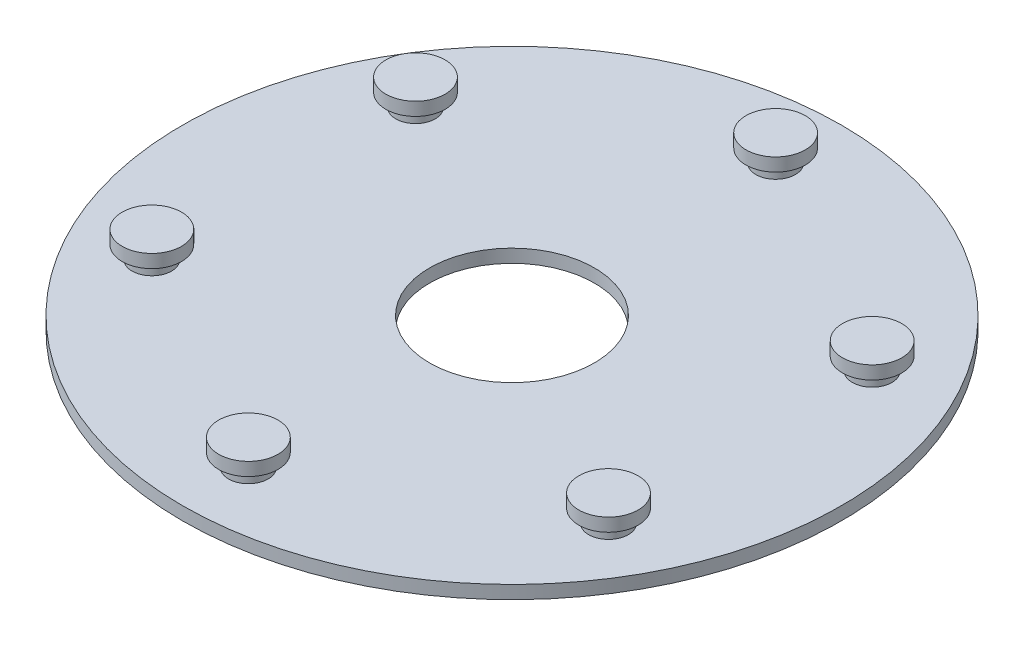
SolidWorks part; units mm, degrees
ref_plane "Front Plane" through (0, 0, 0) normal (0, 0, 1) x (1, 0, 0)
ref_plane "Top Plane" through (0, 0, 0) normal (0, 1, 0) x (1, 0, 0)
ref_plane "Right Plane" through (0, 0, 0) normal (1, 0, 0) x (0, 0, -1)
sketch "Sketch1" plane through (0, 0, 0) normal (0, 1, 0) x (1, 0, 0)
  circle A0 centre (0, 0) radius 50
  dimension "D1" = 100
extrude "Boss-Extrude1" add sketch "Sketch1" along normal blind 2 contours A0
sketch "Sketch2" plane through (0, 2, 0) normal (0, 1, 0) x (1, 0, 0)
  line L0 (0, 50) -> (0, -50) construction
  line L1 (-50, 0) -> (50, 0) construction
  circle A0 centre (0, 0) radius 50 construction
  circle A1 centre (0, -40) radius 4.5
  circle A2 centre (0, 0) radius 40 construction
  circle A3 centre (0, 0) radius 12.5
  circle A4 centre (0, -40) radius 3
  dimension "D1" = 80
  dimension "D2" = 25
  dimension "D3" = 9
  dimension "D4" = 6
extrude "Cut-Extrude1" cut sketch "Sketch2" against normal up to surface (2 mm away) contours A3 up to face at (0, 0, 50)
extrude "Boss-Extrude2" add sketch "Sketch2<3>" along normal blind 4 contours A1
sketch "Sketch2<3>" plane through (0, 2, 0) normal (0, 1, 0) x (1, 0, 0) same geometry as "Sketch2"
extrude "Cut-Extrude2" cut sketch "Sketch2<4>" along normal blind 2 contours A4 | A1
sketch "Sketch2<4>" plane through (0, 2, 0) normal (0, 1, 0) x (1, 0, 0) same geometry as "Sketch2"
pattern_circular "CirPattern1" count 12 every 30 about axis through (0, -35.3553, 0) along (0, 1, 0) skipping 1, 3, 5, 7, 9, 11 of "Boss-Extrude2", "Cut-Extrude2"
sketch "Sketch4" plane through (0, 2, 0) normal (0, 1, 0) x (1, 0, 0)
  line L0 (0, 50) -> (0, -50) construction
  line L1 (-50, 0) -> (50, 0) construction
  circle A0 centre (0, 0) radius 50 construction
